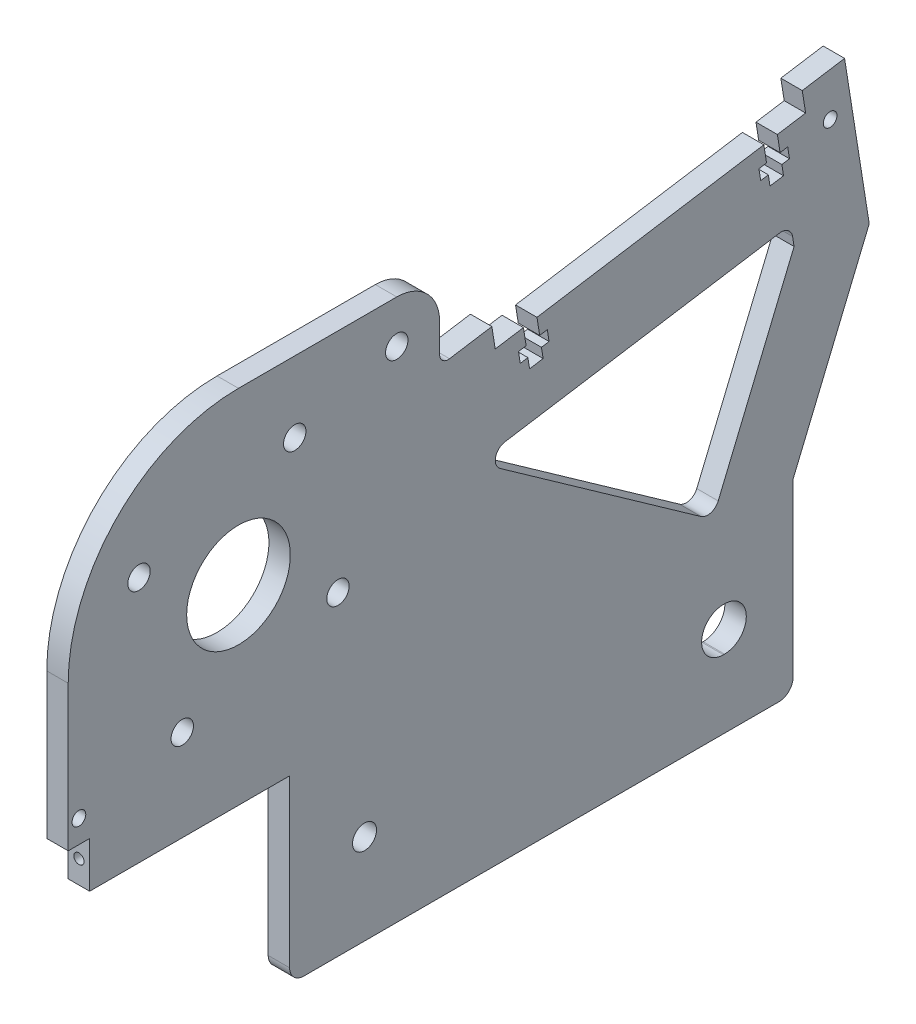
SolidWorks part; units mm, degrees
ref_plane "Front Plane" through (0, 0, 0) normal (0, 0, 1) x (1, 0, 0)
ref_plane "Top Plane" through (0, 0, 0) normal (0, 1, 0) x (1, 0, 0)
ref_plane "Right Plane" through (0, 0, 0) normal (1, 0, 0) x (0, 0, -1)
sketch "Sketch1" plane through (0, 0, 0) normal (1, 0, 0) x (0, 0, -1)
  line L0 (-28.1703, 0) -> (77.3828, 0)
  line L1 (80.5578, 3.175) -> (80.5578, 41.307)
  line L2 (-80.5578, 82.55) -> (-80.5578, 50.292)
  line L3 (4.1952, 102.6435) -> (13.6029, 104.1335)
  line L4 (-75.7953, 50.292) -> (-75.7953, 40.132)
  line L5 (-80.5578, 50.292) -> (-75.7953, 50.292)
  line L6 (65.3178, 20.066) -> (65.0638, 20.066) construction
  line L7 (-75.7953, 40.132) -> (-31.3453, 40.132)
  line L8 (1.9922, 110.875) -> (1.9922, 104.525)
  line L9 (-42.7078, 120.4) -> (-7.5328, 120.4)
  line L10 (-31.3453, 40.132) -> (-31.3453, 3.175)
  line L11 (-37.7935, 96.5728) -> (77.9184, 56.022) construction
  line L12 (-52.4128, 71.2982) -> (40.4331, -8.7847) construction
  line L13 (65.3178, 15.2273) -> (65.0638, 15.2273)
  line L14 (65.3178, 24.9047) -> (65.0638, 24.9047)
  line L15 (4.1952, 102.6435) -> (101.0919, 102.6435) construction
  line L16 (13.6029, 104.1335) -> (14.348, 99.4297)
  line L17 (14.348, 99.4297) -> (20.6198, 100.423)
  line L18 (83.338, 110.3566) -> (82.593, 115.0605)
  line L19 (82.593, 115.0605) -> (92.0007, 116.5505)
  line L20 (92.0007, 116.5505) -> (97.4765, 81.978)
  line L21 (97.4765, 81.978) -> (80.5578, 41.307)
  line L22 (20.6198, 100.423) -> (21.2208, 96.6286)
  line L23 (21.2208, 96.6286) -> (19.5274, 96.3604)
  line L24 (19.5274, 96.3604) -> (19.9198, 93.883)
  line L25 (19.9198, 93.883) -> (21.6131, 94.1512)
  line L26 (26.317, 94.8962) -> (25.9246, 97.3736)
  line L27 (25.9246, 97.3736) -> (24.2312, 97.1054)
  line L28 (24.2312, 97.1054) -> (23.6303, 100.8998)
  line L29 (23.6303, 100.8998) -> (74.0557, 108.8864)
  line L30 (77.0662, 109.3632) -> (83.338, 110.3566)
  line L31 (80.4436, 88.0391) -> (80.7745, 85.9497)
  line L38 (21.6131, 94.1512) -> (21.9857, 91.7993)
  line L39 (21.9857, 91.7993) -> (24.9961, 92.2761)
  line L40 (24.9961, 92.2761) -> (24.6236, 94.628)
  line L41 (24.6236, 94.628) -> (26.317, 94.8962)
  line L46 (74.0557, 108.8864) -> (74.6567, 105.092)
  line L47 (77.5375, 90.1504) -> (16.5054, 80.4839)
  line L48 (15.4361, 75.9014) -> (60.0992, 44.3133)
  line L49 (63.9111, 45.4115) -> (80.7745, 85.9497)
  line L50 (74.6567, 105.092) -> (72.9633, 104.8238)
  line L51 (72.9633, 104.8238) -> (73.3557, 102.3464)
  line L52 (73.3557, 102.3464) -> (75.0491, 102.6146)
  line L53 (79.7529, 103.3596) -> (79.3605, 105.837)
  line L54 (79.3605, 105.837) -> (77.6672, 105.5688)
  line L55 (77.6672, 105.5688) -> (77.0662, 109.3632)
  line L56 (75.0491, 102.6146) -> (75.4216, 100.2627)
  line L57 (75.4216, 100.2627) -> (78.432, 100.7395)
  line L58 (78.432, 100.7395) -> (78.0595, 103.0914)
  line L59 (78.0595, 103.0914) -> (79.7529, 103.3596)
  arc A0 (65.3178, 15.2273) -> (65.3178, 24.9047) centre (65.3178, 20.066) ccw
  circle A1 centre (-42.7078, 82.55) radius 31.5 construction
  circle A2 centre (65.3178, 20.066) radius 78.105 construction
  circle A3 centre (65.3178, 20.066) radius 38.1 construction
  circle A4 centre (-42.7078, 82.55) radius 14.859 construction
  arc A5 (-42.7078, 120.4) -> (-80.5578, 82.55) centre (-42.7078, 82.55) ccw
  arc A6 (-28.1703, 0) -> (-31.3453, 3.175) centre (-28.1703, 3.175) cw
  arc A7 (77.3828, 0) -> (80.5578, 3.175) centre (77.3828, 3.175) ccw
  circle A9 centre (-7.5328, 110.875) radius 6.35 construction
  circle A10 centre (-55.209, 60.4394) radius 2.4892
  circle A11 centre (-14.6922, 20.066) radius 2.667
  circle A12 centre (-20.5972, 70.0488) radius 2.4892
  circle A13 centre (-64.8184, 95.0512) radius 2.4892
  circle A14 centre (-30.2065, 104.6606) radius 2.4892
  circle A15 centre (-78.1765, 55.372) radius 1.524
  circle A16 centre (-42.7078, 82.55) radius 11.5228
  arc A17 (65.0638, 24.9047) -> (65.0638, 15.2273) centre (65.0638, 20.066) ccw
  arc A18 (-7.5328, 120.4) -> (1.9922, 110.875) centre (-7.5328, 110.875) cw
  circle A19 centre (-7.5328, 110.875) radius 2.4892
  arc A20 (4.1952, 102.6435) -> (1.9922, 104.525) centre (3.8972, 104.525) cw
  circle A22 centre (88.7869, 106.3978) radius 1.524
  arc A24 (60.0992, 44.3133) -> (63.9111, 45.4115) centre (61.5659, 46.387) ccw
  arc A25 (16.5054, 80.4839) -> (15.4361, 75.9014) centre (16.9028, 77.9752) ccw
  arc A26 (77.5375, 90.1504) -> (80.4436, 88.0391) centre (77.9349, 87.6417) cw
  point P39 (65.1908, 20.066)
  dimension "D4" = 9.6774
  dimension "D7" = 29.718
  dimension "D8" = 63
  dimension "D9" = 6.35
  dimension "D12" = 3.175
  dimension "D13" = 4.7625
  dimension "D14" = 76.2
  dimension "D15" = 156.21
  dimension "D18" = 5.334
  dimension "D19" = 9.525
  dimension "D20" = 9.525
  dimension "D23" = 3.048
  dimension "D27" = 73.025
  dimension "D28" = 12.7
  dimension "D29" = 4.9784
  dimension "D31" = 1.905
  dimension "D33" = 3.048
  dimension "D42" = 2.54
  dimension "D44" = 86.36
  dimension "D48" = 3.048
  dimension "D49" = 9.525
  dimension "D2" = 40.132
  dimension "D3" = 20.066
  dimension "D5" = 15.24
  dimension "D6" = 44.45
  dimension "D10" = 161.1156
  dimension "D11" = 95.25
  dimension "D17" = 9
  dimension "D21" = 4.7625
  dimension "D22" = 10.16
  dimension "D24" = 5.08
  dimension "D25" = 2.3813
  dimension "D26" = 0.254
  dimension "D16" = 88.9
  dimension "D30" = 9.525
  dimension "D34" = 19.05
  dimension "D35" = 8.7312
  dimension "D36" = 2.5083
  dimension "D37" = 6.477
  dimension "D38" = 6.35
  dimension "D40" = 15.875
  dimension "D45" = 6.35
  dimension "D46" = 6.35
  dimension "D47" = 4.7625
  dimension "D50" = 5.08
  dimension "D39" = 2
extrude "Boss-Extrude1" add sketch "Sketch1" along normal blind 4.7625
sketch "Sketch2" plane through (0, 0, 75.7953) normal (0, 0, 1) x (1, 0, 0)
  line L0 (4.7625, 50.292) -> (4.7625, 40.132) construction
  line L1 (4.7625, 40.132) -> (0, 40.132) construction
  circle A0 centre (2.3813, 45.212) radius 1.1303
  point P4 (4.7625, 45.212)
  point P7 (2.3813, 40.132)
  dimension "D1" = 2.2606
extrude "Cut-Extrude1" cut sketch "Sketch2" against normal blind 6.35
